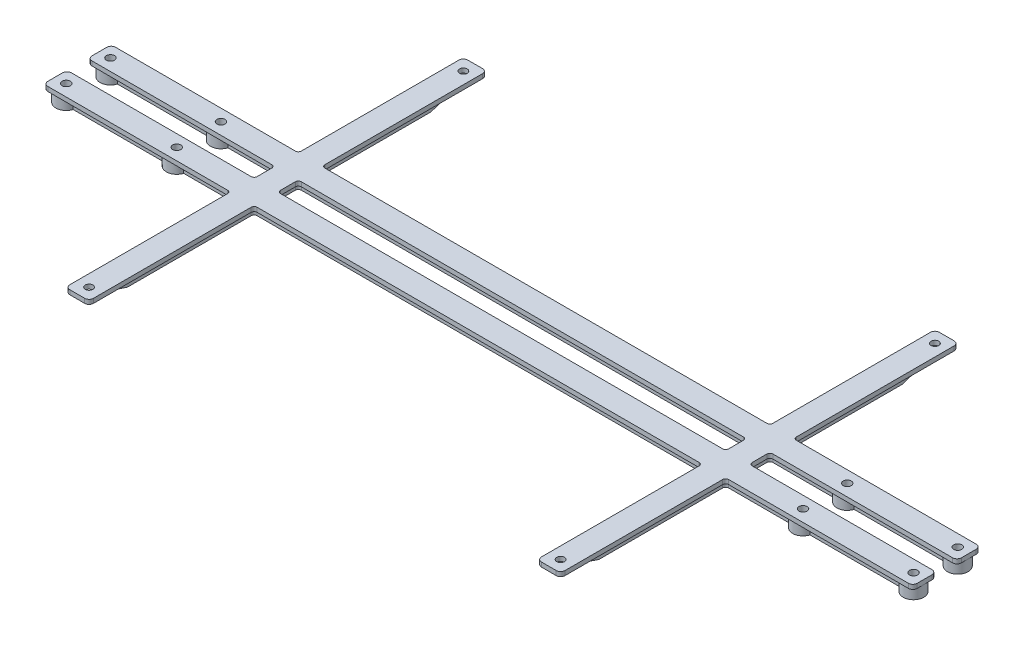
SolidWorks part; units mm, degrees
material "7075-T6，板材(SS)"
ref_plane "前视基准面" through (0, 0, 0) normal (0, 0, 1) x (1, 0, 0)
ref_plane "上视基准面" through (0, 0, 0) normal (0, 1, 0) x (1, 0, 0)
ref_plane "右视基准面" through (0, 0, 0) normal (1, 0, 0) x (0, 0, -1)
sketch "草图1" plane through (0, 0, 0) normal (0, 0, 1) x (1, 0, 0)
  line L0 (-295, 0) -> (295, 0)
  line L1 (-285, -8) -> (285, -8)
  line L2 (0, -8) -> (0, 0) construction
  line L3 (-295, 0) -> (-295, -3)
  line L4 (-295, -3) -> (-285, -8)
  line L5 (295, -3) -> (285, -8)
  line L6 (295, 0) -> (295, -3)
  point P4 (0, 0)
  dimension "D1" = 590
  dimension "D2" = 8
  dimension "D3" = 570
  dimension "D4" = 3
extrude "凸台-拉伸1" add sketch "草图1" along normal mid plane 4
sketch "草图3" plane through (0, 0, 0) normal (0, 0, 1) x (1, 0, 0)
  line L0 (295, 0) -> (295, 3)
  line L1 (295, 3) -> (-295, 3)
  line L2 (-295, 3) -> (-295, 0)
  line L3 (-295, 0) -> (295, 0)
  dimension "D1" = 3
extrude "凸台-拉伸3" add sketch "草图3" along normal mid plane 16
sketch "草图4" plane through (0, 3, 0) normal (0, 1, 0) x (1, 0, 0)
  line L1 (-275, -10) -> (275, -10) construction
  line L2 (-275, -10) -> (-275, 10) construction
  line L3 (-275, 10) -> (275, 10) construction
  line L4 (275, -10) -> (275, 10) construction
  line L5 (-275, -10) -> (275, 10) construction
  line L6 (-275, 10) -> (275, -10) construction
  circle A0 centre (275, 10) radius 3.5
  circle A1 centre (275, -10) radius 3.5
  circle A2 centre (-275, -10) radius 3.5
  circle A3 centre (-275, 10) radius 3.5
  point P0 (0, 0)
  dimension "D3" = 7
  dimension "D1" = 20
  dimension "D2" = 550
extrude "凸台-拉伸4" add sketch "草图4" against normal up to surface (3 mm away) up to face at (0, 0, -5)
fillet "圆角2" [suppressed] radius 3
sketch "草图5" plane through (0, 3, 0) normal (0, 1, 0) x (1, 0, 0)
  line L1 (-140, -10) -> (140, -10) construction
  line L2 (-140, -10) -> (-140, 10) construction
  line L3 (-140, 10) -> (140, 10) construction
  line L4 (140, -10) -> (140, 10) construction
  line L5 (-140, -10) -> (140, 10) construction
  line L6 (-140, 10) -> (140, -10) construction
  circle A0 centre (140, -10) radius 3.5 construction
  circle A1 centre (140, 10) radius 3.5
  circle A2 centre (-140, 10) radius 3.5
  circle A3 centre (-140, -10) radius 3.5 construction
  circle A4 centre (0, 10) radius 3.5 construction
  circle A5 centre (0, -10) radius 3.5 construction
  point P0 (0, 0)
  dimension "D3" = 7
  dimension "D1" = 280
  dimension "D2" = 20
extrude "凸台-拉伸5" add sketch "草图5" against normal up to surface (3 mm away) up to face at (0, 0, -7.875)
fillet "圆角3" radius 3 4 edges at (142.8723, 1.5, -8) (137.1277, 1.5, -8) (-137.1277, 1.5, -8) (-142.8723, 1.5, -8)
sketch "草图6" plane through (0, 3, 0) normal (0, 1, 0) x (1, 0, 0)
  circle A0 centre (275, 10) radius 1.6
  circle A1 centre (275, -10) radius 1.6
  circle A2 centre (140, 10) radius 1.6
  circle A3 centre (140, -10) radius 1.6
  circle A4 centre (0, 10) radius 1.6 construction
  circle A5 centre (0, -10) radius 1.6 construction
  circle A6 centre (-140, 10) radius 1.6
  circle A7 centre (-140, -10) radius 1.6
  circle A8 centre (-275, 10) radius 1.6
  circle A9 centre (-275, -10) radius 1.6
  dimension "D1" = 3.2
extrude "切除-拉伸1" cut sketch "草图6" against normal through all
fillet "圆角4" radius 3 4 edges at (295, 1.5, 8) (295, 1.5, -8) (-295, 1.5, -8) (-295, 1.5, 8)
ref_plane "基准面1" through (0, 0, 90) normal (0, 0, 1) x (1, 0, 0)
ref_plane "基准面2" through (0, 0, 15) normal (0, 0, 1) x (1, 0, 0)
sketch "草图7" plane through (0, 0, 0) normal (0, 1, 0) x (1, 0, 0)
  line L0 (-160, 100) -> (-160, -130) construction
  line L1 (-168, 100) -> (-168, -130)
  line L2 (-152, 100) -> (-152, -130)
  line L3 (-168, 100) -> (-152, 100)
  line L4 (-168, -130) -> (-152, -130)
  point P2 (-160, -15)
  dimension "D1" = 15
  dimension "D2" = 160
  dimension "D3" = 230
  dimension "D4" = 8
  dimension "D5" = 8
extrude "凸台-拉伸6" add sketch "草图7" along normal up to surface (3 mm away) contours L3 L0 L4 L2 | L0 L3 L1 L4 up to face at (-141.6, 3, -10)
mirror "镜向1" about plane through (0, 0, 15) normal (0, 0, 1) of "凸台-拉伸3", "凸台-拉伸4", "凸台-拉伸5", "切除-拉伸1"
fillet "圆角5" [suppressed] radius 3
fillet "圆角6" [suppressed] radius 3
mirror "镜向2" about plane through (0, 0, 15) normal (0, 0, 1) of "凸台-拉伸1"
fillet "圆角7" [suppressed] radius 3
sketch "草图8" plane through (0, 0, 0) normal (0, -1, 0) x (1, 0, 0)
  line L0 (-160, 130) -> (-160, -100) construction
  line L1 (-168, 130) -> (-152, 130) construction
  line L2 (-168, -100) -> (-152, -100) construction
  line L3 (-162, 130) -> (-162, -100)
  line L4 (-158, 130) -> (-158, -100)
  line L5 (-162, 130) -> (-158, 130)
  line L6 (-162, -100) -> (-158, -100)
  dimension "D1" = 2
  dimension "D2" = 2
extrude "凸台-拉伸7" add sketch "草图8" along normal up to surface (8 mm away) up to face at (0, -8, 30)
sketch "草图9" plane through (-162, 0, 0) normal (-1, 0, 0) x (0, 0, 1)
  line L0 (130, -4) -> (118, -8)
  line L1 (130, -8) -> (130, 0) construction
  line L2 (130, -8) -> (32, -8) construction
  line L3 (118, -8) -> (130, -8)
  line L4 (130, -8) -> (130, -4)
  dimension "D1" = 12
extrude "切除-拉伸2" cut sketch "草图9" against normal through all
mirror "镜向3" about plane through (0, 0, 0) normal (1, 0, 0) of "凸台-拉伸7", "凸台-拉伸6"
sketch "草图11" plane through (-162, 0, 0) normal (-1, 0, 0) x (0, 0, 1)
  line L0 (15, 3) -> (15, -28.394) construction
  line L1 (22, 3) -> (8, 3) construction
  line L2 (118, -8) -> (130, -4)
  line L3 (130, -4) -> (130, -8)
  line L4 (130, -8) -> (118, -8)
  line L5 (-100, -8) -> (-88, -8)
  line L6 (-100, -4) -> (-100, -8)
  line L7 (-88, -8) -> (-100, -4)
extrude "切除-拉伸3" cut sketch "草图11" against normal through all
fillet "圆角8" [suppressed] radius 3
ref_plane "基准面3" through (160, 0, 0) normal (-1, 0, 0) x (0, 0, 1)
ref_plane "基准面4" through (-160, 0, 0) normal (1, 0, 0) x (0, 0, -1)
fillet "圆角9" [suppressed] radius 3
fillet "圆角10" [suppressed] radius 2
fillet "圆角11" [suppressed] radius 2
sketch "草图12" [suppressed] plane through (0, 3, 0) normal (0, 1, 0) x (1, 0, 0)
  line L0 (0, -10) -> (0, -20) construction
  line L1 (149, -109) -> (171, -109) construction
  line L2 (149, -109) -> (149, 79) construction
  line L3 (149, 79) -> (171, 79) construction
  line L4 (171, -109) -> (171, 79) construction
  line L5 (149, -109) -> (171, 79) construction
  line L6 (149, 79) -> (171, -109) construction
  line L7 (0, -15) -> (160, -15) construction
  line L8 (168, -20) -> (168, -10) construction
  circle A0 centre (171, -109) radius 3.5
  circle A1 centre (149, -109) radius 3.5
  circle A2 centre (171, 79) radius 3.5
  circle A3 centre (149, 79) radius 3.5
  point P0 (160, -15)
  dimension "D4" = 7
  dimension "D1" = 8
  dimension "D2" = 188
  dimension "D3" = 22
extrude "凸台-拉伸8" [suppressed] add sketch "草图12" against normal up to surface (3 mm away)
fillet "圆角12" [suppressed] radius 3
sketch "草图13" [suppressed] plane through (0, 3, 0) normal (0, 1, 0) x (1, 0, 0)
  circle A0 centre (171, 79) radius 1.6
  circle A1 centre (149, 79) radius 1.6
  circle A2 centre (171, -109) radius 1.6
  circle A3 centre (149, -109) radius 1.6
  dimension "D1" = 3.2
extrude "切除-拉伸4" [suppressed] cut sketch "草图13" against normal blind 10
mirror "镜向5" [suppressed] about plane through (0, 0, 0) normal (1, 0, 0)
fillet "圆角13" [suppressed] radius 3
sketch "草图14" plane through (0, 3, 0) normal (0, 1, 0) x (1, 0, 0)
  line L0 (295, -5) -> (295, 5) construction
  line L1 (292, 8) -> (277.8723, 8) construction
  circle A0 centre (287.5, 0) radius 2.6
  dimension "D2" = 5.2
  dimension "D3" = 8
  dimension "D1" = 7.5
extrude "切除-拉伸6" cut sketch "草图14" against normal through all
mirror "镜向6" about plane through (0, 0, 15) normal (0, 0, 1) of "切除-拉伸6"
mirror "镜向7" about plane through (0, 0, 0) normal (1, 0, 0) of "镜向6", "切除-拉伸6"
sketch "草图15" [suppressed] plane through (0, 0, 32) normal (0, 0, 1) x (1, 0, 0)
  line L0 (-295, 0) -> (-283, 0)
  line L1 (-278.4583, 0) -> (-271.5417, 0) construction
  line L2 (-283, 0) -> (-283, -3)
  line L3 (-283, -3) -> (-273, -8)
  line L4 (-285, -8) -> (-164, -8) construction
  line L5 (-273, -8) -> (-285, -8)
  line L6 (-285, -8) -> (-295, -3)
  line L7 (-295, -3) -> (-295, 0)
  dimension "D1" = 12
extrude "切除-拉伸7" [suppressed] cut sketch "草图15" against normal through all
mirror "镜向8" [suppressed] about plane through (0, 0, 0) normal (1, 0, 0)
sketch "草图16" plane through (0, -8, 0) normal (0, -1, 0) x (1, 0, 0)
  line L0 (-212.5, 0) -> (-287.5, 0) construction
  circle A0 centre (-212.5, 0) radius 3
  circle A1 centre (-287.5, 0) radius 2.6 construction
  dimension "D2" = 6
  dimension "D1" = 75
extrude "切除-拉伸8" cut sketch "草图16" against normal up to surface (8 mm away) up to face at (138.4, 0, 40)
mirror "镜向9" about plane through (0, 0, 15) normal (0, 0, 1) of "切除-拉伸8"
mirror "镜向10" about plane through (0, 0, 0) normal (1, 0, 0) of "镜向9", "切除-拉伸8"
sketch "草图18" [suppressed] plane through (0, 0, -2) normal (0, 0, -1) x (-1, 0, 0)
  line L0 (-295, 0) -> (-204, 0)
  line L1 (-210.2639, 0) -> (-162, 0) construction
  line L2 (-204, 0) -> (-204, -3)
  line L3 (-204, -3) -> (-194, -8)
  line L4 (-162, -8) -> (-210.2639, -8) construction
  line L5 (-194, -8) -> (-285, -8)
  line L6 (-285, -8) -> (-295, -3)
  line L7 (-295, -3) -> (-295, 0)
  line L8 (-162, -8) -> (-162, 0) construction
  dimension "D1" = 42
sketch "草图19" plane through (0, 0, 0) normal (0, -1, 0) x (1, 0, 0)
  line L0 (212.5, 30) -> (287.5, 30) construction
  circle A0 centre (212.5, 30) radius 2.6
  dimension "D1" = 5.2
  dimension "D2" = 75
extrude "切除-拉伸11" cut sketch "草图19" against normal blind 48
mirror "镜向11" about plane through (0, 0, 15) normal (0, 0, 1) of "切除-拉伸11"
mirror "镜向12" about plane through (0, 0, 0) normal (1, 0, 0) of "镜向11", "切除-拉伸11"
sketch "草图20" plane through (0, 0, 130) normal (0, 0, 1) x (1, 0, 0)
  line L0 (-168, 3) -> (-152, 3)
  line L1 (-152, 3) -> (-152, 0)
  line L2 (-152, 0) -> (-168, 0)
  line L3 (-168, 0) -> (-168, 3)
extrude "凸台-拉伸9" add sketch "草图20" along normal blind 20
mirror "镜向13" about plane through (0, 0, 0) normal (1, 0, 0) of "凸台-拉伸9"
mirror "镜向14" about plane through (0, 0, 15) normal (0, 0, 1) of "镜向13", "凸台-拉伸9"
sketch "草图21" plane through (0, 0, 0) normal (0, -1, 0) x (1, 0, 0)
  line L0 (-152, 38) -> (-152, 150) construction
  line L1 (-168, 150) -> (-152, 150) construction
  circle A0 centre (-160, 142) radius 2.6
  dimension "D1" = 8
  dimension "D2" = 5.2
  dimension "D3" = 8
extrude "切除-拉伸13" cut sketch "草图21" against normal blind 20
mirror "镜向17" about plane through (0, 0, 0) normal (1, 0, 0) of "切除-拉伸13"
mirror "镜向18" about plane through (0, 0, 15) normal (0, 0, 1) of "镜向17", "切除-拉伸13"
sketch "草图22" plane through (0, 0, 0) normal (0, -1, 0) x (1, 0, 0)
  line L0 (-152, -8) -> (152, -8)
  line L1 (152, -8) -> (152, -28.4586)
  line L2 (152, -120) -> (152, -8) construction
  line L3 (152, -28.4586) -> (-152, -28.4586)
  line L4 (-152, -120) -> (-152, -8) construction
  line L5 (-152, -28.4586) -> (-152, -8)
  line L6 (-152, 53.7598) -> (152, 53.7598)
  line L7 (-152, 38) -> (-152, 150) construction
  line L8 (152, 38) -> (152, 150) construction
  line L9 (152, 53.7598) -> (152, 38)
  line L10 (152, 38) -> (-152, 38)
  line L11 (-152, 38) -> (-152, 53.7598)
  line L12 (-295, 38) -> (-295, 58.6321)
  line L13 (-295, 58.6321) -> (-254.0242, 58.6321)
  line L14 (-254.0242, 58.6321) -> (-254.0242, 38)
  line L15 (-272.1277, 38) -> (-168, 38) construction
  line L16 (-254.0242, 38) -> (-295, 38)
  line L17 (-289.6853, -8) -> (-263.1761, -8)
  line L18 (-292, -8) -> (-277.8723, -8) construction
  line L19 (-272.1277, -8) -> (-168, -8) construction
  line L20 (-263.1761, -8) -> (-265.0696, -21.546)
  line L21 (-265.0696, -21.546) -> (-289.6853, -21.546)
  line L22 (-289.6853, -21.546) -> (-289.6853, -8)
  line L23 (253.3035, 38) -> (253.3035, 62.2459)
  line L24 (168, 38) -> (272.1277, 38) construction
  line L25 (253.3035, 62.2459) -> (291.354, 62.2459)
  line L26 (291.354, 62.2459) -> (291.354, 38)
  line L27 (277.8723, 38) -> (295, 38) construction
  line L28 (291.354, 38) -> (253.3035, 38)
  line L29 (256.0939, -8) -> (256.0939, -25.5239)
  line L30 (168, -8) -> (272.1277, -8) construction
  line L31 (256.0939, -25.5239) -> (293.3834, -25.5239)
  line L32 (293.3834, -25.5239) -> (292, -8)
  line L33 (292, -8) -> (256.0939, -8)
  line L34 (265.5059, 22) -> (288.133, 22)
  line L35 (168, 22) -> (272.1277, 22) construction
  line L36 (277.8723, 22) -> (295, 22) construction
  line L37 (288.133, 22) -> (288.133, 8)
  line L38 (277.8723, 8) -> (292, 8) construction
  line L39 (288.133, 8) -> (263.9394, 8)
  line L40 (168, 8) -> (272.1277, 8) construction
  line L41 (263.9394, 8) -> (265.5059, 22)
  line L42 (-261.3121, 22) -> (-287.7016, 22)
  line L43 (-272.1277, 22) -> (-168, 22) construction
  line L44 (-295, 22) -> (-277.8723, 22) construction
  line L45 (-287.7016, 22) -> (-287.7016, 8)
  line L46 (-292, 8) -> (-277.8723, 8) construction
  line L47 (-287.7016, 8) -> (-262.5158, 8)
  line L48 (-272.1277, 8) -> (-168, 8) construction
  line L49 (-262.5158, 8) -> (-261.3121, 22)
extrude "切除-拉伸14" cut sketch "草图22" against normal through all
fillet "圆角14" radius 3 12 edges at (152, 1.5, -120) (168, 1.5, -120) (295, 1.5, 38) (-295, 1.5, 38) (295, 1.5, 22) (-295, 1.5, 22) (168, 1.5, 150) (152, 1.5, 150) (-168, 1.5, 150) (-152, 1.5, 150) (-152, 1.5, -120) (-168, 1.5, -120)
fillet "圆角15" radius 2 16 edges at (152, 1.5, 38) (152, 1.5, 22) (152, 1.5, -8) (152, 1.5, 8) (168, 1.5, 38) (168, 1.5, -8) (168, 1.5, 22) (168, 1.5, 8) (158, -4, -2) (158, -4, 32) (162, -4, -2) (162, -4, 32) (158, -4, 2) (158, -4, 28) (162, -4, 2) (162, -4, 28)
fillet "圆角16" radius 2 16 edges at (-168, 1.5, -8) (-168, 1.5, 8) (-152, 1.5, -8) (-152, 1.5, 8) (-168, 1.5, 38) (-168, 1.5, 22) (-152, 1.5, 38) (-152, 1.5, 22) (-158, -4, 32) (-162, -4, 32) (-162, -4, 2) (-162, -4, -2) (-162, -4, 28) (-158, -4, 2) (-158, -4, -2) (-158, -4, 28)
sketch "草图23" plane through (0, -8, 0) normal (0, -1, 0) x (1, 0, 0)
  circle A0 centre (-287.5, 30) radius 2.6
  circle A1 centre (-287.5, 30) radius 7
  dimension "D1" = 14
extrude "凸台-拉伸10" add sketch "草图23" against normal up to surface (8 mm away)
sketch "草图24" plane through (0, -8, 0) normal (0, -1, 0) x (1, 0, 0)
  line L0 (-287.5, 35) -> (-299.1153, 35)
  line L1 (-299.1153, 35) -> (-299.1153, 25)
  line L2 (-299.1153, 25) -> (-287.5, 25)
  circle A0 centre (-287.5, 30) radius 5
  arc M2 (-280.7918, 32) -> (-280.7918, 28) centre (-287.5, 30) ccw
extrude "切除-拉伸15" cut sketch "草图24" against normal up to surface (8 mm away) contours L1 L2 L0 M2 up to face at (0, 0, 15)
pattern_linear "阵列(线性)1" count 2 spacing 75 along (1, 0, 0) of "凸台-拉伸10"
mirror "镜向19" about plane through (0, 0, 15) normal (0, 0, 1) of "切除-拉伸15", "阵列(线性)1", "凸台-拉伸10"
mirror "镜向20" about plane through (0, 0, 0) normal (1, 0, 0) of "镜向19", "凸台-拉伸10", "切除-拉伸15", "阵列(线性)1"
hole_wizard "打孔尺寸(%根据)内六角圆柱头螺钉的类型1" positions "3D草图1" profile "草图25" counterbore size "M5" standard "GB"
sketch3d "3D草图1"
  line L3 (-287.5, -8, 30) -> (-287.5, 3, 30) construction
  line L4 (-212.5, 3, 30) -> (-212.5, -8, 30) construction
  line L5 (-212.5, 3, 0) -> (-212.5, -8, 0) construction
  line L6 (-287.5, -8, 0) -> (-287.5, 3, 0) construction
  point P11 (-287.5, -8, 30)
  point P15 (-212.5, -8, 30)
  point P28 (-212.5, -8, 0)
  point P34 (-287.5, -8, 0)
sketch "草图25" plane through (-287.5, -8, 30) normal (1, 0, 0) x (0, 0, -1)
  line L0 (0, 0) -> (0, 21.6524)
  line L1 (0, 21.6524) -> (2.75, 20)
  line L2 (2.75, 20) -> (2.75, 5.7)
  line L3 (2.75, 5.7) -> (5, 5.7)
  line L4 (5, 5.7) -> (5, 0)
  line L5 (5, 0) -> (0, 0)
  line L10 (0, 21.6524) -> (-2.75, 20) construction
  line L11 (0, -6.35) -> (0, 107.95) construction
  dimension "孔直径" = 5.5
  dimension "孔深度" = 20
  dimension "柱形沉头孔直径" = 10
  dimension "柱形沉头孔深度" = 5.7
  dimension "导头角度" = 118
mirror "镜向21" about plane through (0, 0, 0) normal (1, 0, 0) of "打孔尺寸(%根据)内六角圆柱头螺钉的类型1"
